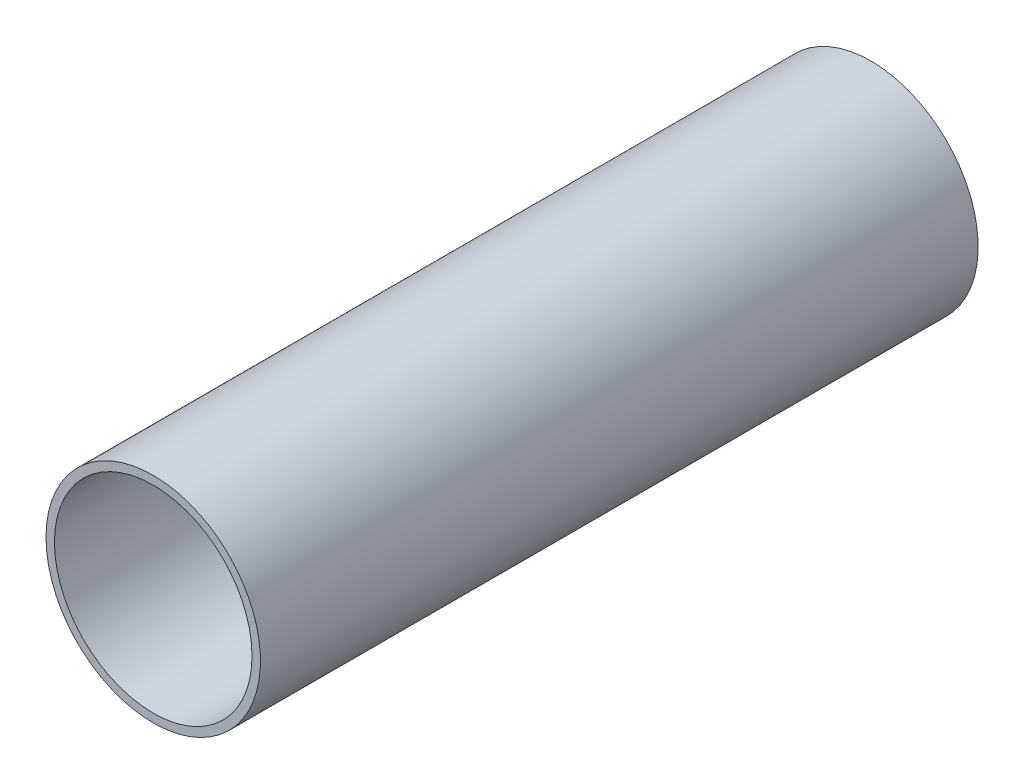
SolidWorks part; units mm, degrees
ref_plane "Front Plane" through (0, 0, 0) normal (0, 0, 1) x (1, 0, 0)
ref_plane "Top Plane" through (0, 0, 0) normal (0, 1, 0) x (1, 0, 0)
ref_plane "Right Plane" through (0, 0, 0) normal (1, 0, 0) x (0, 0, -1)
sketch "Path" plane through (0, 0, 0) normal (1, 0, 0) x (0, 0, -1)
  line L0 (0, 0) -> (85, 0)
  dimension "Longitud" = 85
sweep "Sweep-Thin" add path "Path" circular profile diameter 1 parameters "Espesor"=1, "Diámetro"=25.4
